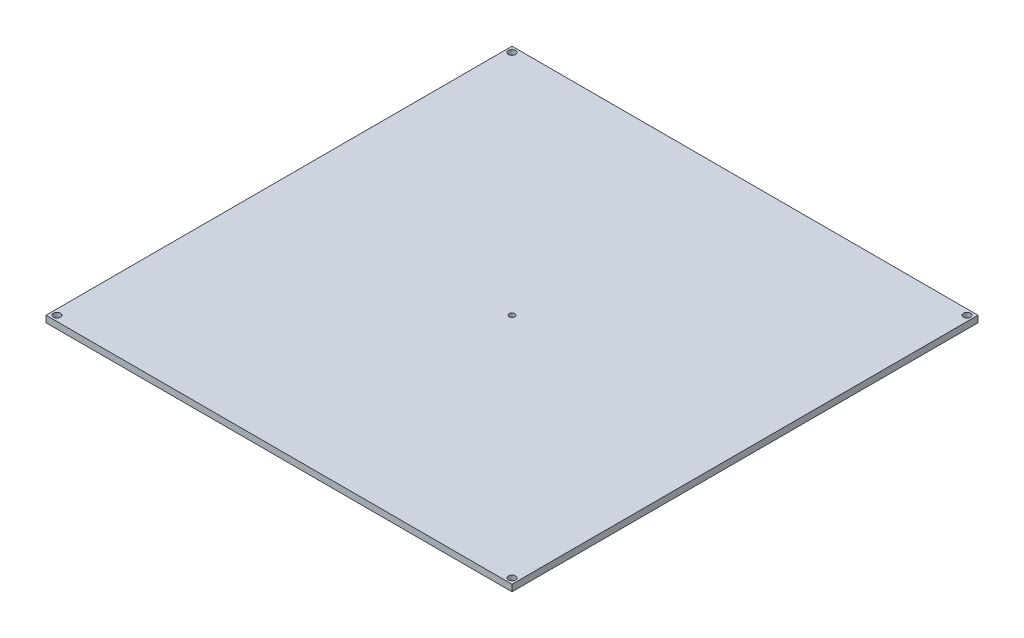
SolidWorks part; units mm, degrees
material "1060 Alloy"
ref_plane "Front Plane" through (0, 0, 0) normal (0, 0, 1) x (1, 0, 0)
ref_plane "Top Plane" through (0, 0, 0) normal (0, 1, 0) x (1, 0, 0)
ref_plane "Right Plane" through (0, 0, 0) normal (1, 0, 0) x (0, 0, -1)
sketch "Sketch1" plane through (0, 0, 0) normal (0, 1, 0) x (1, 0, 0)
  line L1 (-106.75, -106.75) -> (106.75, -106.75)
  line L2 (-106.75, -106.75) -> (-106.75, 106.75)
  line L3 (-106.75, 106.75) -> (106.75, 106.75)
  line L4 (106.75, -106.75) -> (106.75, 106.75)
  line L5 (-106.75, -106.75) -> (106.75, 106.75) construction
  line L6 (-106.75, 106.75) -> (106.75, -106.75) construction
  point P0 (0, 0)
  dimension "D1" = 213.5
  dimension "D2" = 213.5
base flange "Base-Flange1" sketch "Sketch1" thickness 3 reverse thickness direction no parameters "D1"=1.75
hole_wizard "Ø3.0mm Clearance Dowel Hole1" positions "Sketch12" profile "Sketch11" hole size "Ø3.0" standard "ANSI Metric" end condition through all
sketch "Sketch12" plane through (0, 0, 0) normal (0, 1, 0) x (1, 0, 0)
  line L0 (-106.75, -106.75) -> (106.75, -106.75) construction
  line L1 (-106.75, 106.75) -> (-106.75, -106.75) construction
  line L2 (106.75, 106.75) -> (-106.75, 106.75) construction
  point P0 (-104.25, 104.25)
  point P2 (-104.25, -104.25)
  dimension "D1" = 2.5
  dimension "D2" = 2.5
  dimension "D3" = 2.5
  dimension "D4" = 2.5
sketch "Sketch11" plane through (-104.25, 0, -104.25) normal (1, 0, 0) x (0, 0, 1)
  line L0 (0, 0) -> (0, 3)
  line L1 (0, 3) -> (1.6, 3)
  line L2 (1.6, 3) -> (1.6, 0)
  line L5 (1.6, 0) -> (0, 0)
  line L11 (0, -6.35) -> (0, 107.95) construction
  dimension "Thru Hole Dia." = 3.2
  dimension "Thru Hole Depth" = 3
mirror "Mirror2" about plane through (0, 0, 0) normal (1, 0, 0) of "Ø3.0mm Clearance Dowel Hole1"
hole_wizard "Ø2.5mm Clearance Dowel Hole1" positions "Sketch14" profile "Sketch13" hole size "Ø2.5" standard "ANSI Metric" end condition through all
sketch "Sketch14" plane through (0, 0, 0) normal (0, 1, 0) x (1, 0, 0)
  point P0 (0, 0)
sketch "Sketch13" plane through (0, 0, 0) normal (1, 0, 0) x (0, 0, 1)
  line L0 (0, 0) -> (0, 3)
  line L1 (0, 3) -> (1.25, 3)
  line L2 (1.25, 3) -> (1.25, 0)
  line L5 (1.25, 0) -> (0, 0)
  line L11 (0, -6.35) -> (0, 107.95) construction
  dimension "Thru Hole Dia." = 2.5
  dimension "Thru Hole Depth" = 3
sketch "Bend-Lines1" [suppressed] plane through (0, 0, 0) normal (0, 1, 0) x (1, 0, 0)
sketch "Bounding-Box1" [suppressed] plane through (0, 0, 0) normal (0, 1, 0) x (1, 0, 0)
sheet metal parameters "Sheet-Metal1" thickness 3 parameters "D1"=1.75
flat pattern "Flat-Pattern1" [suppressed]
sketch "Bend-Lines2" plane through (0, 0, 0) normal (0, 1, 0) x (1, 0, 0)
sketch3d "Bounding-Box2" [suppressed]
  line L0 (-106.5, -106.5, 0) -> (-106.5, 106.5, 0) construction
  line L1 (106.5, -106.5, 0) -> (106.5, 106.5, 0) construction
  line L2 (-106.5, -106.5, 0) -> (106.5, -106.5, 0) construction
  line L3 (-106.5, 106.5, 0) -> (106.5, 106.5, 0) construction
sheet metal parameters "Sheet-Metal4" thickness 3 parameters "D1"=1.75
flat pattern "Flat-Pattern1"
sketch "Bend-Lines2" plane through (0, 0, 0) normal (0, 1, 0) x (1, 0, 0)
sketch3d "Bounding-Box2" [suppressed]
  line L0 (-106.5, -106.5, 0) -> (-106.5, 106.5, 0) construction
  line L1 (106.5, -106.5, 0) -> (106.5, 106.5, 0) construction
  line L2 (-106.5, -106.5, 0) -> (106.5, -106.5, 0) construction
  line L3 (-106.5, 106.5, 0) -> (106.5, 106.5, 0) construction
sheet metal parameters "Sheet-Metal5" thickness 3 parameters "D1"=1.75
flat pattern "Flat-Pattern1"
sketch "Bend-Lines2" plane through (0, 0, 0) normal (0, 1, 0) x (1, 0, 0)
sketch3d "Bounding-Box2" [suppressed]
  line L0 (-106.75, -106.75, 0) -> (-106.75, 106.75, 0) construction
  line L1 (106.75, -106.75, 0) -> (106.75, 106.75, 0) construction
  line L2 (-106.75, -106.75, 0) -> (106.75, -106.75, 0) construction
  line L3 (-106.75, 106.75, 0) -> (106.75, 106.75, 0) construction
sheet metal parameters "Sheet-Metal6" thickness 3 parameters "D1"=1.75
flat pattern "Flat-Pattern1"
sketch "Bend-Lines2" plane through (0, 0, 0) normal (0, 1, 0) x (1, 0, 0)
sketch3d "Bounding-Box2" [suppressed]
  line L0 (-106.75, -106.75, 0) -> (-106.75, 106.75, 0) construction
  line L1 (106.75, -106.75, 0) -> (106.75, 106.75, 0) construction
  line L2 (-106.75, -106.75, 0) -> (106.75, -106.75, 0) construction
  line L3 (-106.75, 106.75, 0) -> (106.75, 106.75, 0) construction
